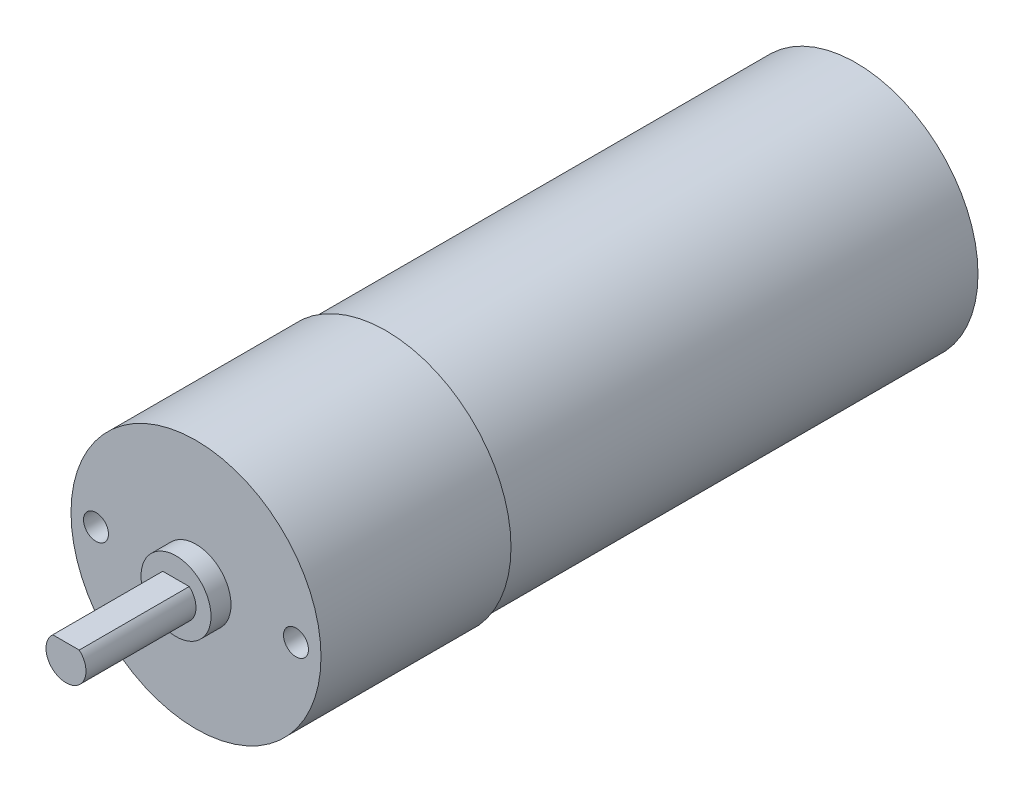
SolidWorks part; units mm, degrees
ref_plane "Front Plane" through (0, 0, 0) normal (0, 0, 1) x (1, 0, 0)
ref_plane "Top Plane" through (0, 0, 0) normal (0, 1, 0) x (1, 0, 0)
ref_plane "Right Plane" through (0, 0, 0) normal (1, 0, 0) x (0, 0, -1)
sketch "Sketch1" plane through (0, 0, 0) normal (0, 0, 1) x (1, 0, 0)
  circle A0 centre (0, 0) radius 12.2
  circle A1 centre (0, 0) radius 12.5
  dimension "D1" = 24.4
  dimension "D2" = 25
extrude "Boss-Extrude1" add sketch "Sketch1" along normal blind 47 contours A0 region at (0, 0, 0)
extrude "Boss-Extrude2" add sketch "Sketch1<3>" along normal blind 19 from surface contours A0 | A1 A0 region at (0, 0, 0) region at (-12.4646, 0, 0) starting at face at (12.2, 0, 47)
sketch "Sketch1<3>" plane through (0, 0, 0) normal (0, 0, 1) x (1, 0, 0) same geometry as "Sketch1"
sketch "Sketch2" plane through (0, 0, 66) normal (0, 0, 1) x (1, 0, 0)
  line L0 (-1.3229, 1.5) -> (1.3229, 1.5)
  circle A0 centre (0, 0) radius 3.5
  circle A1 centre (0, 0) radius 2
  dimension "D1" = 7
  dimension "D2" = 4
  dimension "D3" = 0.5
extrude "Boss-Extrude4" add sketch "Sketch2" along normal blind 2 contours L0 A1 | L0 A1 | A0 A1 region at (0, 1.7023, 66) region at (0, -0.1324, 66) region at (-3.401, 0, 66)
extrude "Boss-Extrude5" add sketch "Sketch2<4>" along normal blind 11 from surface contours L0 A1 region at (0, -0.1324, 66) starting at face at (3.5, 0, 68)
sketch "Sketch2<4>" plane through (0, 0, 66) normal (0, 0, 1) x (1, 0, 0) same geometry as "Sketch2"
sketch "Sketch3" plane through (0, 0, 66) normal (0, 0, 1) x (1, 0, 0)
  line L0 (0, 12.5) -> (0, -12.5) construction
  circle A0 centre (0, 0) radius 12.5 construction
  circle A1 centre (10, 0) radius 1.5
  circle A2 centre (-10, 0) radius 1.5
  point P7 (9.8572, -1.6837)
  dimension "D1" = 3
  dimension "D2" = 10
hole_wizard "M3x0.5 Tapped Hole1" positions "3DSketch1" profile "Sketch4" tap size "M3x0.5" standard "ANSI Metric"
sketch3d "3DSketch1"
  point P0 (-10, 0, 66)
  point P3 (10, 0, 66)
sketch "Sketch4" plane through (-10, 0, 66) normal (1, 0, 0) x (0, -1, 0)
  line L0 (0, 0) -> (0, 8.2511)
  line L1 (0, 8.2511) -> (1.25, 7.5)
  line L2 (1.25, 7.5) -> (1.25, 0)
  line L5 (1.25, 0) -> (0, 0)
  line L10 (0, 8.2511) -> (-1.25, 7.5) construction
  line L11 (0, -6.35) -> (0, 107.95) construction
  dimension "Tap Drill Dia." = 2.5
  dimension "Tap Drill Depth" = 7.5
  dimension "Drill Angle" = 118
